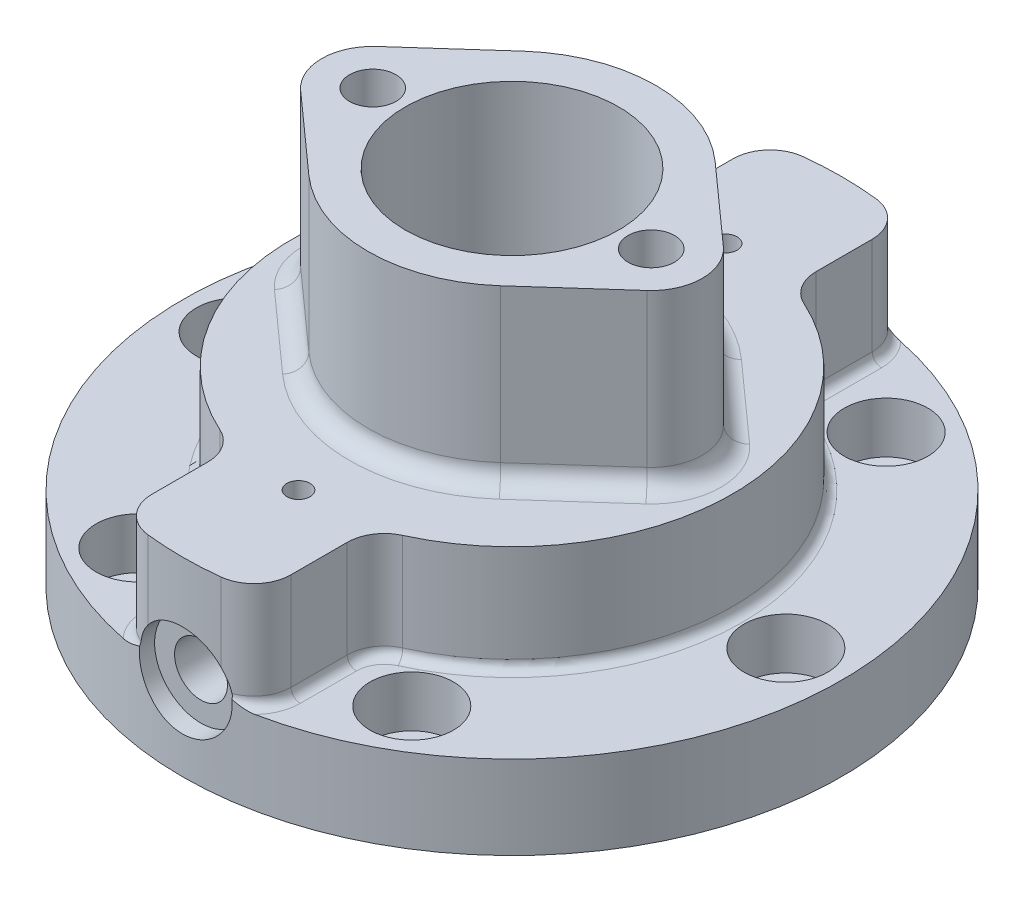
SolidWorks part; units mm, degrees
ref_plane "Piano frontale" through (0, 0, 0) normal (0, 0, 1) x (1, 0, 0)
ref_plane "Piano superiore" through (0, 0, 0) normal (0, 1, 0) x (1, 0, 0)
ref_plane "Piano destro" through (0, 0, 0) normal (1, 0, 0) x (0, 0, -1)
sketch "Schizzo1" plane through (0, 0, 0) normal (0, 0, 1) x (1, 0, 0)
  line L0 (0, 26.9483) -> (0, -22.0992) construction
  line L1 (-7.5, 16) -> (-7.5, 20.5)
  line L2 (-7.5, 20.5) -> (-35.5, 20.5)
  line L3 (-35.5, 20.5) -> (-35.5, 0)
  line L4 (-35.5, 0) -> (-15.5, 0)
  line L5 (-15.5, 0) -> (-15.5, 9)
  line L6 (-15.5, 9) -> (-12.5, 9)
  line L7 (-12.5, 9) -> (-8.4585, 16)
  line L8 (-8.4585, 16) -> (-7.5, 16)
  point P5 (-8.1272, 19.0501)
  dimension "D1" = 71
  dimension "D2" = 31
  dimension "D3" = 25
  dimension "D4" = 30
  dimension "D5" = 15
  dimension "D6" = 20.5
  dimension "D7" = 9
  dimension "D8" = 7
revolve "Rivoluzione1" add sketch "Schizzo1" angle 360 about L0
sketch "Schizzo2" plane through (0, 20.5, 0) normal (0, 1, 0) x (1, 0, 0)
  line L0 (0, 41.0513) -> (0, -42.596) construction
  line L1 (-7.5, 34.6987) -> (-7.5, 22.5347)
  line L2 (-7.5, -34.6987) -> (-7.5, -22.5347)
  line L3 (7.5, -34.6987) -> (7.5, -22.5347)
  line L4 (7.5, 34.6987) -> (7.5, 22.5347)
  circle A0 centre (0, 0) radius 35.5 construction
  arc A1 (-7.5, 22.5347) -> (-7.5, -22.5347) centre (0, 0) ccw
  arc A2 (7.5, 22.5347) -> (7.5, -22.5347) centre (0, 0) cw
  arc A3 (-7.5, 34.6987) -> (7.5, 34.6987) centre (0, 0) cw
  arc A4 (-7.5, -34.6987) -> (7.5, -34.6987) centre (0, 0) ccw
  dimension "D1" = 47.5
  dimension "D3" = 35.5
  dimension "D4" = 35.5
  dimension "D2" = 15
sketch "Schizzo3" plane through (0, 20.5, 0) normal (0, 1, 0) x (1, 0, 0)
  line L0 (-18.6667, 4.0995) -> (-10.3333, 11.553)
  line L1 (-49.7547, 0) -> (46.0284, 0) construction
  line L2 (-18.6667, -4.0995) -> (-10.3333, -11.553)
  line L3 (10.3333, 11.553) -> (18.6667, 4.0995)
  line L4 (10.3333, -11.553) -> (18.6667, -4.0995)
  line L5 (0, 0) -> (0, 23.7664) construction
  circle A0 centre (0, 0) radius 11.5
  arc A1 (-10.3333, -11.553) -> (10.3333, -11.553) centre (0, 0) ccw
  arc A2 (-18.6667, 4.0995) -> (-18.6667, -4.0995) centre (-15, 0) ccw
  arc A4 (10.3333, 11.553) -> (-10.3333, 11.553) centre (0, 0) ccw
  arc A5 (18.6667, 4.0995) -> (18.6667, -4.0995) centre (15, 0) cw
  point P8 (0, 0)
  point P16 (9.0491, -11.5)
  point P17 (0, 0)
  dimension "D1" = 23
  dimension "D2" = 30
  dimension "D3" = 5.5
  dimension "D4" = 15.5
extrude "Estrusione-Estrusione1" add sketch "Schizzo3" along normal blind 18.5
extrude "Taglio-Estrusione3" cut sketch "Schizzo2" against normal blind 11.5 flip side to cut
fillet "Raccordo2" radius 4 8 edges at (-7.5, 14.75, -22.5347) (-7.5, 14.75, -34.6987) (7.5, 14.75, -34.6987) (7.5, 14.75, -22.5347) (7.5, 14.75, 22.5347) (-7.5, 14.75, 22.5347) (7.5, 14.75, 34.6987) (-7.5, 14.75, 34.6987)
fillet "Raccordo3" radius 1 14 edges at (-6.4814, 9, 33.9716) (-7.5, 9, 28.28) (-8.1362, 9, 23.0905) (-23.75, 9, 0) (-8.1362, 9, -23.0905) (-7.5, 9, -28.28) (-6.4814, 9, -33.9716) (8.1362, 9, 23.0905) (7.5, 9, 28.28) (6.4814, 9, 33.9716) (6.4814, 9, -33.9716) (7.5, 9, -28.28) (8.1362, 9, -23.0905) (23.75, 9, 0)
fillet "Raccordo4" radius 2 8 edges at (14.5, 20.5, -7.8262) (0, 20.5, -15.5) (-14.5, 20.5, -7.8262) (20.5, 20.5, 0) (14.5, 20.5, 7.8262) (-20.5, 20.5, 0) (-14.5, 20.5, 7.8262) (0, 20.5, 15.5)
hole_wizard "Foro Ø5.0 (5)-1" positions "Schizzo4" profile "Schizzo5" hole size "Ø5.0" standard "ISO"
sketch "Schizzo4" plane through (0, 39, 0) normal (0, 1, 0) x (1, 0, 0)
  line L0 (0, 26.9814) -> (0, -26.6844) construction
  line L1 (0, 0) -> (-25.4549, 0) construction
  point P18 (-15, 0)
  point P21 (15, 0)
  dimension "D1" = 30
sketch "Schizzo5" plane through (15, 39, 0) normal (1, 0, 0) x (0, 0, 1)
  line L0 (0, 0) -> (0, 9.0022)
  line L1 (0, 9.0022) -> (2.5, 7.5)
  line L2 (2.5, 7.5) -> (2.5, 0)
  line L5 (2.5, 0) -> (0, 0)
  line L10 (0, 9.0022) -> (-2.5, 7.5) construction
  line L11 (0, -6.35) -> (0, 107.95) construction
  dimension "Hole Dia." = 5
  dimension "Hole Depth" = 7.5
  dimension "Drill Angle" = 118
ref_point "Punto1"
ref_plane "Piano1" through (0, 0, 35.5) normal (0, 0, 1) x (1, 0, 0)
hole_wizard "Foro Ø2.5 (2.5)-1" positions "Schizzo6" profile "Schizzo7" hole size "Ø2.5" standard "ISO"
sketch "Schizzo6" plane through (0, 0, 35.5) normal (0, 0, 1) x (1, 0, 0)
  line L0 (-35.5, 0) -> (35.5, 0) construction
  point P0 (0, 9)
  dimension "D1" = 9
sketch "Schizzo7" plane through (0, 9, 35.5) normal (1, 0, 0) x (0, -1, 0)
  line L0 (0, 0) -> (0, 36.2501)
  line L1 (0, 36.2501) -> (1.25, 35.499)
  line L2 (1.25, 35.499) -> (1.25, 0)
  line L5 (1.25, 0) -> (0, 0)
  line L10 (0, 36.2501) -> (-1.25, 35.499) construction
  line L11 (0, -6.35) -> (0, 107.95) construction
  dimension "Hole Dia." = 2.5
  dimension "Hole Depth" = 35.499
  dimension "Drill Angle" = 118
hole_wizard "Foro lamato per Bullone M5 a testa esagonale-1" positions "Schizzo8" profile "Schizzo9" counterbore size "M5" standard "ISO"
sketch "Schizzo8" plane through (0, 0, 35.5) normal (0, 0, 1) x (1, 0, 0)
  line L0 (-15.5, 9) -> (15.5, 9) construction
  point P0 (0, 9)
sketch "Schizzo9" plane through (0, 9, 35.5) normal (1, 0, 0) x (0, -1, 0)
  line L0 (0, 0) -> (0, 17.7125)
  line L1 (0, 17.7125) -> (2.85, 16)
  line L2 (2.85, 16) -> (2.85, 2)
  line L3 (2.85, 2) -> (5, 2)
  line L4 (5, 2) -> (5, 0)
  line L5 (5, 0) -> (0, 0)
  line L10 (0, 17.7125) -> (-2.85, 16) construction
  line L11 (0, -6.35) -> (0, 107.95) construction
  dimension "Hole Dia." = 5.7
  dimension "Hole Depth" = 16
  dimension "C'Bore Dia." = 10
  dimension "C'Bore Depth" = 2
  dimension "Drill Angle" = 118
mirror "Specchia2" about plane through (0, 0, 0) normal (0, 0, 1) of "Foro Ø2.5 (2.5)-1", "Foro lamato per Bullone M5 a testa esagonale-1"
hole_wizard "Foro Ø2.5 (2.5)-2" positions "Schizzo10" profile "Schizzo11" hole size "Ø2.5" standard "ISO" end condition up to next
sketch "Schizzo10" plane through (0, 20.5, 0) normal (0, 1, 0) x (1, 0, 0)
  line L0 (-41.0909, 0) -> (59.8047, 0) construction
  point P0 (0, 23)
  point P7 (0, -23)
  dimension "D1" = 46
sketch "Schizzo11" plane through (0, 20.5, -23) normal (1, 0, 0) x (0, 0, 1)
  line L0 (0, 0) -> (0, 8.65)
  line L1 (0, 8.65) -> (1.25, 8.65)
  line L2 (1.25, 8.65) -> (1.25, 0)
  line L5 (1.25, 0) -> (0, 0)
  line L11 (0, -6.35) -> (0, 107.95) construction
  dimension "Thru Hole Dia." = 2.5
  dimension "Thru Hole Depth" = 8.65
hole_wizard "Foro lamato per Bullone M5 a testa esagonale-2" positions "Schizzo12" profile "Schizzo13" counterbore size "M5" standard "ISO" end condition up to next
sketch "Schizzo12" plane through (0, 9, 0) normal (0, 1, 0) x (1, 0, 0)
  line L0 (0, 0) -> (29.5, 0) construction
  circle A0 centre (0, 0) radius 29.5 construction
  point P7 (29.5, 0)
  dimension "D1" = 59
sketch "Schizzo13" plane through (29.5, 9, 0) normal (1, 0, 0) x (0, 0, 1)
  line L0 (0, 0) -> (0, 9)
  line L1 (0, 9) -> (2.75, 9)
  line L3 (2.75, 9) -> (2.75, 5.5)
  line L4 (2.75, 5.5) -> (4.5, 5.5)
  line L5 (4.5, 5.5) -> (4.5, 0)
  line L7 (4.5, 0) -> (0, 0)
  line L11 (0, -6.35) -> (0, 107.95) construction
  dimension "Thru Hole Dia." = 5.5
  dimension "Thru Hole Depth" = 9
  dimension "C'Bore Dia." = 9
  dimension "C'Bore Depth" = 5.5
pattern_circular "RipetizioneCircolare1" count 6 over 360 about axis through (0, 39, 0) along (0, -1, 0) of "Foro lamato per Bullone M5 a testa esagonale-2" reverse direction yes
sketch "Schizzo14" plane through (0, 0, 0) normal (0, -1, 0) x (1, 0, 0)
  line L0 (0, 0) -> (0, 36.3153)
